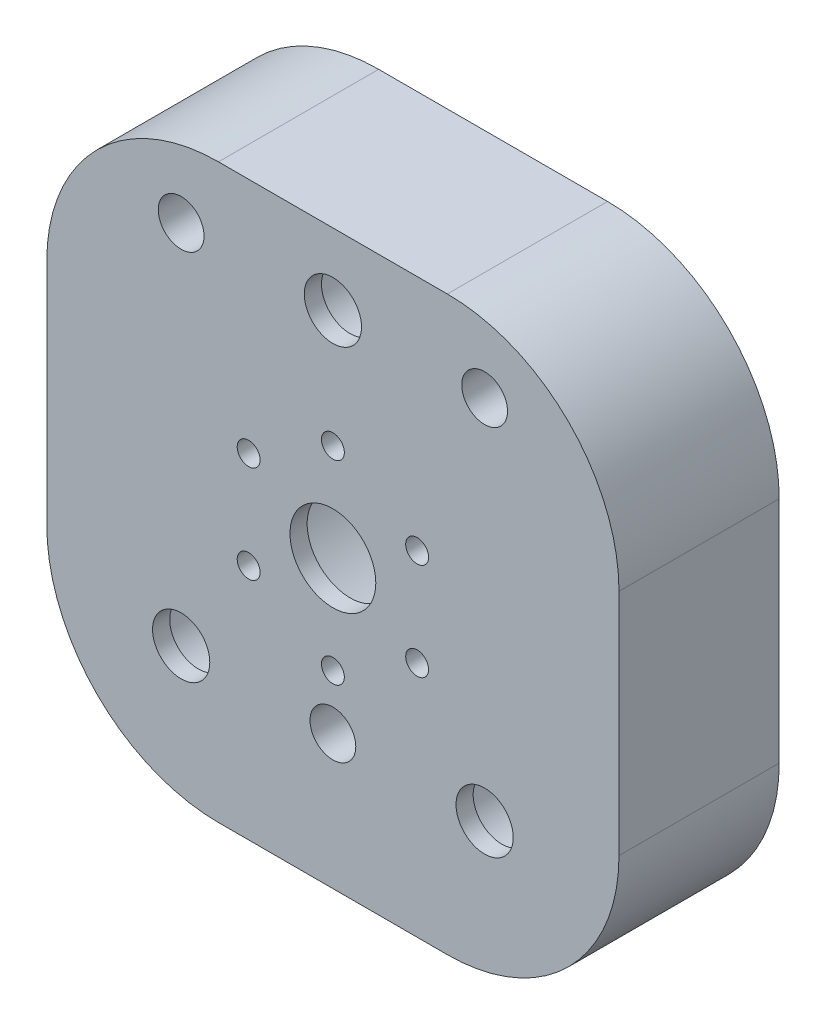
SolidWorks part; units mm, degrees
ref_plane "Front Plane" through (0, 0, 0) normal (0, 0, 1) x (1, 0, 0)
ref_plane "Top Plane" through (0, 0, 0) normal (0, 1, 0) x (1, 0, 0)
ref_plane "Right Plane" through (0, 0, 0) normal (1, 0, 0) x (0, 0, -1)
sketch "Sketch1" plane through (0, 0, 0) normal (0, 0, 1) x (1, 0, 0)
  line L5 (-50, 50) -> (50, 50)
  line L6 (-50, 50) -> (-50, -50)
  line L7 (-50, -50) -> (50, -50)
  line L8 (50, 50) -> (50, -50)
  circle A4 centre (-14.7224, 8.5) radius 2 construction
  circle A5 centre (-14.7224, -8.5) radius 2 construction
  circle A6 centre (0, -17) radius 2 construction
  circle A7 centre (14.7224, -8.5) radius 2 construction
  circle A8 centre (14.7224, 8.5) radius 2 construction
  circle A9 centre (0, 17) radius 2 construction
  circle A10 centre (-14.7224, 8.5) radius 2
  circle A11 centre (-14.7224, -8.5) radius 2
  circle A12 centre (0, -17) radius 2
  circle A13 centre (14.7224, -8.5) radius 2
  circle A14 centre (14.7224, 8.5) radius 2
  circle A15 centre (0, 17) radius 2
  circle A16 centre (0, 0) radius 7.5
  circle A17 centre (0, 37.5) radius 5
  circle A18 centre (-26.5165, -26.5165) radius 5
  circle A19 centre (26.5165, -26.5165) radius 5
  point P5 (0, 50)
  point P7 (0, 0)
  point P17 (-50, 0)
  dimension "D3" = 10
  dimension "D5" = 15
  dimension "D1" = 100
  dimension "D2" = 100
extrude "Boss-Extrude1" add sketch "Sketch1" along normal blind 3
sketch "Sketch2" plane through (0, 0, 0) normal (0, 0, -1) x (-1, 0, 0)
  circle A0 centre (0, 37.5) radius 8.1
  circle A1 centre (26.5165, -26.5165) radius 8.1
  circle A2 centre (-26.5165, -26.5165) radius 8.1
  circle A3 centre (0, 0) radius 22
  line M4 (50, -50) -> (50, 50)
  line M6 (50, 50) -> (-50, 50)
  line M8 (-50, 50) -> (-50, -50)
  line M10 (-50, -50) -> (50, -50)
  dimension "D1" = 16.2
  dimension "D2" = 44
extrude "Boss-Extrude2" add sketch "Sketch2" along normal up to surface (25 mm away) contours A3 A2 A1 A0 M4 M6 M8 M10 region at (0, -48.5858, 0)
fillet "Fillet2" radius 3 3 edges at (-26.5165, -34.6165, -25) (0, 29.4, -25) (26.5165, -34.6165, -25)
fillet "Fillet3" radius 3 1 edges at (0, -22, -25)
sketch "Sketch3" plane through (0, 0, 3) normal (0, 0, 1) x (1, 0, 0)
  circle A0 centre (26.5165, 37.5) radius 4
  circle A1 centre (-26.5165, 37.5) radius 4
  circle A2 centre (0, -26.5165) radius 4
  point P6 (0, 0)
  point P8 (0, 0)
  point P9 (0, 0)
  point P11 (0, 0)
  point P12 (0, 0)
  point P14 (5.1978, -26.5165)
  dimension "D1" = 8
extrude "Cut-Extrude1" cut sketch "Sketch3" against normal offset from surface (25 mm away) 3 up to face at (0, -25, -25)
fillet "Fillet4" radius 30 4 edges at (50, -50, -11) (-50, -50, -11) (-50, 50, -11) (50, 50, -11)
